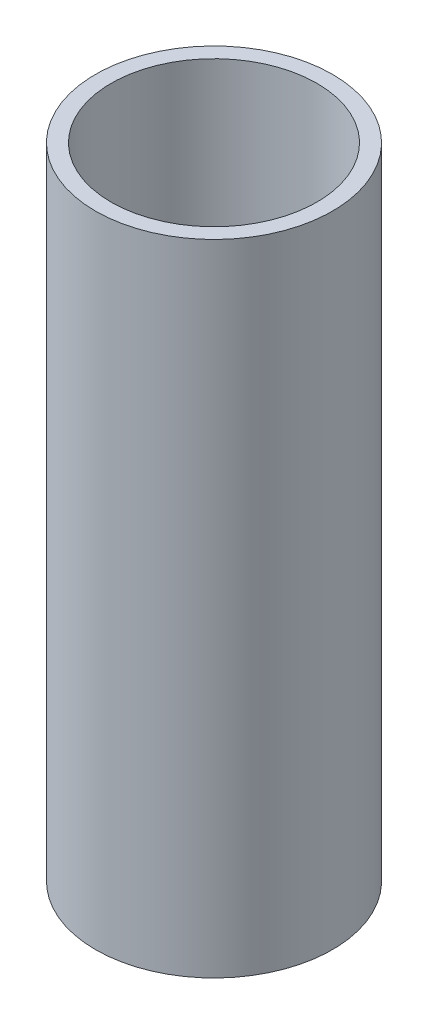
SolidWorks part; units mm, degrees
ref_plane "Front Plane" through (0, 0, 0) normal (0, 0, 1) x (1, 0, 0)
ref_plane "Top Plane" through (0, 0, 0) normal (0, 1, 0) x (1, 0, 0)
ref_plane "Right Plane" through (0, 0, 0) normal (1, 0, 0) x (0, 0, -1)
sketch "Sketch1" plane through (0, 0, 0) normal (0, 1, 0) x (1, 0, 0)
  circle A0 centre (0, 0) radius 21.082
  dimension "D1" = 42.164
extrude "Boss-Extrude1" add sketch "Sketch1" along normal blind 113.792
sketch "Sketch5" plane through (0, 113.792, 0) normal (0, 1, 0) x (1, 0, 0)
  circle A0 centre (0, 0) radius 18.3134
  dimension "D1" = 36.6268
extrude "Cut-Extrude2" cut sketch "Sketch5" against normal blind 111.0234
sketch "Sketch7" plane through (0, 0, 0) normal (0, -1, 0) x (1, 0, 0)
  circle A0 centre (0, 0) radius 6.35
  dimension "D1" = 12.7
extrude "Boss-Extrude2" add sketch "Sketch7" along normal blind 10.16
thread "Thread1" pitch 1.27 method cut profile "Thread Profile1" start angle 0, offset 0, length 0, pitch 1.27, diameter 12.7
ref_plane "Plane1" through (6.35, -10.16, 0) normal (0, 0, 1) x (1, 0, 0)
sketch "Thread Profile1" plane through (6.35, -10.16, 0) normal (0, 0, 1) x (1, 0, 0)
  line L0 (0, 0) -> (0, 1.27) construction
  line L11 (0, 0) -> (0, 1.1112)
  line L12 (0, 1.1112) -> (-0.6874, 0.7144)
  line L13 (-0.6874, 0.7144) -> (-0.6874, 0.3969)
  line L15 (-0.6874, 0.3969) -> (0, 0)
  line L17 (-0.6874, 0.5556) -> (0, 0.5556) construction
  point P2 (0, 0)
  dimension "Pitch" = 1.27
  dimension "Profile_Angle" = 60
  dimension "Profile_Land" = 0.3175
  dimension "Profile_Height" = 0.6874
sketch "Sketch19" plane through (0, -10.16, 0) normal (0, -1, 0) x (1, 0, 0)
  circle A0 centre (0, 0) radius 4.445
  dimension "D1" = 8.89
extrude "Cut-Extrude3" cut sketch "Sketch19" against normal through all
